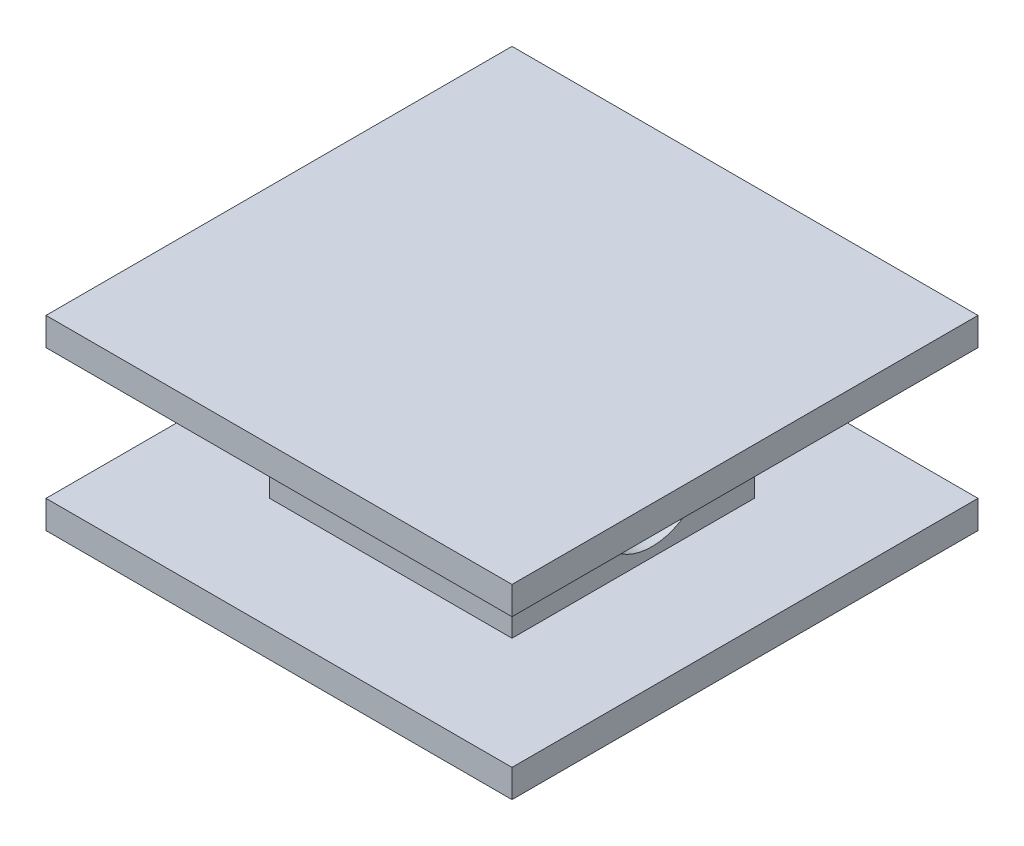
SolidWorks part; units mm, degrees
material "黄铜"
ref_plane "前视基准面" through (0, 0, 0) normal (0, 0, 1) x (1, 0, 0)
ref_plane "上视基准面" through (0, 0, 0) normal (0, 1, 0) x (1, 0, 0)
ref_plane "右视基准面" through (0, 0, 0) normal (1, 0, 0) x (0, 0, -1)
sketch "草图1" plane through (0, 0, 0) normal (0, 1, 0) x (1, 0, 0)
  line L0 (19.4299, 0) -> (-14.6763, 0) construction
  line L1 (-12.5, -12.5) -> (12.5, -12.5)
  line L2 (-12.5, -12.5) -> (-12.5, 12.5)
  line L3 (-12.5, 12.5) -> (12.5, 12.5)
  line L4 (12.5, -12.5) -> (12.5, 12.5)
  line L5 (0, 18.2089) -> (0, -15.1777) construction
  dimension "D1" = 25
  dimension "D2" = 25
extrude "拉伸1" add sketch "草图1" along normal blind 5 and the other way blind 5
sketch "草图8" plane through (-12.5, 0, 0) normal (1, 0, 0) x (0, 0, -1)
  line L0 (-12.5, 5) -> (-12.5, -5) construction
  line L1 (-12.5, 3.5) -> (12.5, 3.5)
  line L2 (-12.5, 3.5) -> (-12.5, -3.5)
  line L3 (-12.5, -3.5) -> (12.5, -3.5)
  line L4 (12.5, 3.5) -> (12.5, -3.5)
  line L5 (12.5, 5) -> (12.5, -5) construction
  line L8 (-17.0887, 0) -> (16.9088, 0) construction
  dimension "D1" = 7
extrude "切除-拉伸8" cut sketch "草图8" along normal blind 6
mirror "镜向1" about plane through (0, 0, 0) normal (1, 0, 0) of "切除-拉伸8"
sketch "草图9" plane through (0, 0, 12.5) normal (0, 0, 1) x (1, 0, 0)
  line L1 (-12.5, 3.5) -> (12.5, 3.5)
  line L2 (-12.5, 3.5) -> (-12.5, -3.5)
  line L3 (-12.5, -3.5) -> (12.5, -3.5)
  line L4 (12.5, 3.5) -> (12.5, -3.5)
extrude "切除-拉伸9" cut sketch "草图9" against normal blind 6
mirror "镜向2" about plane through (0, 0, 0) normal (0, 0, 1) of "切除-拉伸9"
sketch "草图2" plane through (-6.5, 0, 0) normal (1, 0, 0) x (0, 0, -1)
  line L0 (-8.5393, 0) -> (9.1685, 0) construction
  line L1 (1, 11.0674) -> (1, -2.4607) construction
  line L4 (-12.5, 5) -> (12.5, 5) construction
  line L5 (-12.5, -5) -> (12.5, -5) construction
  circle A0 centre (1, 0) radius 3.5
  dimension "D3" = 7
  dimension "D1" = 1
extrude "切除-拉伸1" cut sketch "草图2" along normal blind 10
sketch "草图4" plane through (-6.5, 0, 0) normal (1, 0, 0) x (0, 0, -1)
  line L0 (-7.834, 0) -> (7.1785, 0) construction
  line L1 (-12.5, 5) -> (12.5, 5) construction
  line L2 (-12.5, -5) -> (12.5, -5) construction
  line L3 (-3.3, 7.9182) -> (-3.3, 2.1442) construction
  line L5 (1, 2.7998) -> (1, 6.4518) construction
  circle A0 centre (-3.3, 0) radius 1.25
  dimension "D2" = 4.3
  dimension "D1" = 2.5
extrude "切除-拉伸3" cut sketch "草图4" along normal blind 6
sketch "草图7" plane through (3.5, 0, 0) normal (-1, 0, 0) x (0, 0, 1)
  circle A0 centre (-1, 0) radius 3
  dimension "D1" = 6
extrude "切除-拉伸7" cut sketch "草图7" against normal through all
